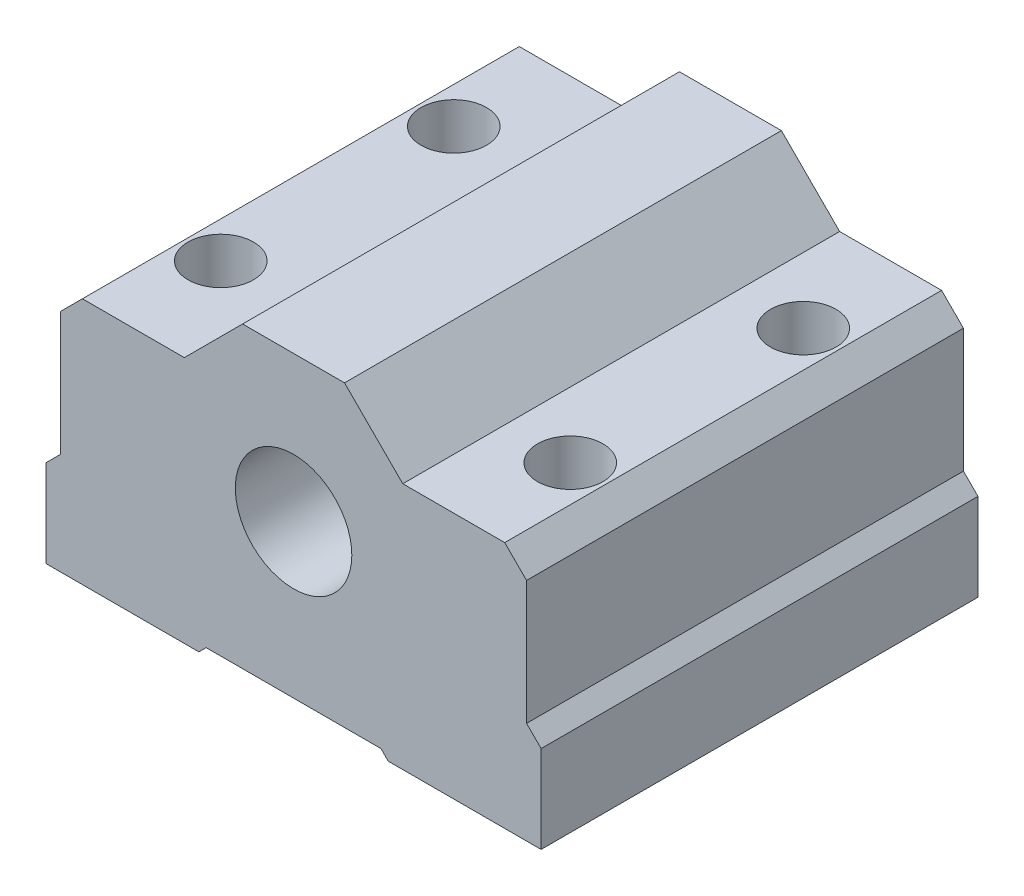
SolidWorks part; units mm, degrees
ref_plane "Face" through (0, 0, 0) normal (0, 0, 1) x (1, 0, 0)
ref_plane "Dessus" through (0, 0, 0) normal (0, 1, 0) x (1, 0, 0)
ref_plane "Droite" through (0, 0, 0) normal (1, 0, 0) x (0, 0, -1)
sketch "Esquisse1" plane through (0, 0, 0) normal (0, 0, 1) x (1, 0, 0)
  line L0 (-17, -11) -> (-6.5, -11)
  line L1 (-6.5, -11) -> (-6, -10.5)
  line L2 (-6, -10.5) -> (6, -10.5)
  line L3 (6, -10.5) -> (6.5, -11)
  line L4 (6.5, -11) -> (17, -11)
  line L5 (17, -11) -> (17, -5)
  line L6 (17, -5) -> (16, -4)
  line L7 (16, -4) -> (16, 4.5)
  line L8 (16, 4.5) -> (14.5, 6)
  line L9 (14.5, 6) -> (7.5, 6)
  line L10 (7.5, 6) -> (3.5, 10)
  line L11 (3.5, 10) -> (-3.5, 10)
  line L12 (-3.5, 10) -> (-7.5, 6)
  line L13 (-7.5, 6) -> (-14.5, 6)
  line L14 (-14.5, 6) -> (-16, 4.5)
  line L15 (-16, 4.5) -> (-16, -4)
  line L16 (-16, -4) -> (-17, -5)
  line L17 (-17, -5) -> (-17, -11)
  line L18 (0, 10) -> (0, -10.5) construction
  line L19 (-8.8582, 0) -> (8.8582, 0) construction
  circle A0 centre (0, 0) radius 4
  point P3 (17, -8)
  point P28 (0, 0)
  dimension "D2" = 8
  dimension "D1" = 21
  dimension "D3" = 34
  dimension "D4" = 0.5
  dimension "D5" = 4
  dimension "D6" = 32
  dimension "D7" = 11
  dimension "D8" = 7
  dimension "D9" = 12
  dimension "D10" = 6
  dimension "D11" = 7
extrude "Boss.-Extru.1" add sketch "Esquisse1" along normal blind 15 and the other way blind 15 contours L16 L17 L0 L1 L2 L3 L4 L5 L6 L7 L9 L10 L11 L12 L13 L15 A0 region at (-16.6004, -8, 0)
sketch "Esquisse perçage" plane through (0, 6, 0) normal (0, -1, 0) x (-1, 0, 0)
  line L0 (12, -8) -> (-12, -8) construction
  line L1 (-12, -8) -> (-12, 8) construction
  line L2 (-12, 8) -> (12, 8) construction
  line L3 (12, 8) -> (12, -8) construction
  line L4 (0, -8) -> (0, 8) construction
  line L5 (12, 0) -> (-12, 0) construction
  point P8 (0, 0)
  dimension "D1" = 24
  dimension "D2" = 16
hole_wizard "Dégagement M41" positions "Esquisse3" profile "Esquisse5" hole size "M4" standard "ISO" end condition through all
sketch "Esquisse3" plane through (0, 6, 0) normal (0, 1, 0) x (1, 0, 0)
  point P0 (-12, 8)
  point P3 (12, 8)
  point P6 (12, -8)
  point P9 (-12, -8)
sketch "Esquisse5" plane through (-12, 6, -8) normal (1, 0, 0) x (0, 0, 1)
  line L0 (0, 0) -> (0, 17)
  line L1 (0, 17) -> (2.25, 17)
  line L2 (2.25, 17) -> (2.25, 0)
  line L5 (2.25, 0) -> (0, 0)
  line L11 (0, -6.35) -> (0, 107.95) construction
  dimension "Diamètre du perçage jusqu'au prochain" = 4.5
  dimension "Profondeur du perçage jusqu'au prochain" = 17
